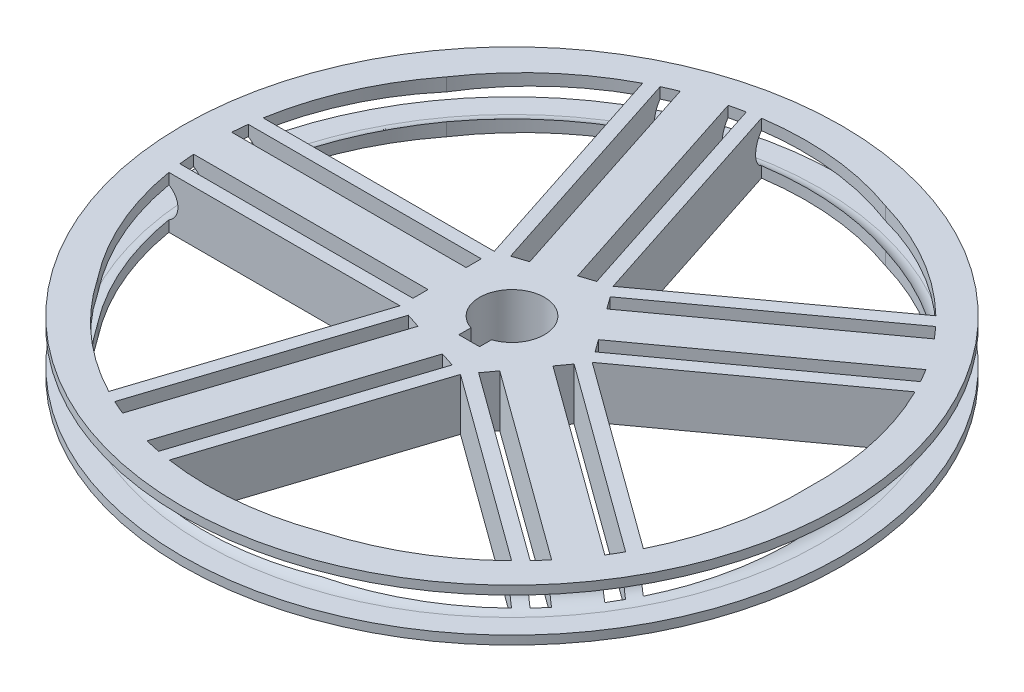
SolidWorks part; units mm, degrees
material "6061 Alloy"
ref_plane "Front Plane" through (0, 0, 0) normal (0, 0, 1) x (1, 0, 0)
ref_plane "Top Plane" through (0, 0, 0) normal (0, 1, 0) x (1, 0, 0)
ref_plane "Right Plane" through (0, 0, 0) normal (1, 0, 0) x (0, 0, -1)
sketch "Sketch1" plane through (0, 0, 0) normal (0, 0, 1) x (1, 0, 0)
  line L3 (0, 8) -> (-5, 8)
  line L4 (0, 0) -> (-5, 0)
  line L5 (-5, 8) -> (-5, 10)
  line L6 (-5, 10) -> (71.2, 10)
  line L7 (0, 4) -> (7.1457, 4) construction
  line L8 (-5, 0) -> (-5, -2)
  line L9 (-5, -2) -> (71.2, -2)
  line L10 (71.2, 10) -> (71.2, -2)
  arc A1 (0, 8) -> (0, 0) centre (0, 4) cw
  dimension "D2" = 4
  dimension "D1" = 8
  dimension "D3" = 5
  dimension "D4" = 5
  dimension "D5" = 76.2
  dimension "D6" = 2
revolve "Revolve2" add sketch "Sketch1" angle 360 about L10
sketch "Sketch2" plane through (0, -2, 0) normal (0, -1, 0) x (1, 0, 0)
  line L5 (71.2, 0) -> (128.6984, 0) construction
  circle A0 centre (71.2, 0) radius 7.5
  dimension "D1" = 15
extrude "Cut-Extrude3" cut sketch "Sketch2" against normal through all
sketch "Sketch3" plane through (0, -2, 0) normal (0, -1, 0) x (1, 0, 0)
  line L0 (71.2, 0) -> (130.5671, 0) construction
  line L2 (89.741, 0) -> (76.9295, 17.6336)
  line L3 (76.9295, 17.6336) -> (56.2, 10.8981)
  line L4 (56.2, 10.8981) -> (56.2, -10.8981)
  line L5 (56.2, -10.8981) -> (76.9295, -17.6336)
  line L6 (76.9295, -17.6336) -> (89.741, 0)
  line L7 (71.2, 0) -> (76.9295, 17.6336)
  line L8 (76.9295, 17.6336) -> (92.3803, 65.1864)
  line L9 (71.2, 0) -> (89.741, 0)
  line L10 (89.741, 0) -> (139.741, 0)
  line L11 (80.7501, 12.3749) -> (124.5759, 44.2162)
  line L12 (85.9204, 5.2586) -> (129.7462, 37.0999)
  line L13 (76.9295, 17.6336) -> (120.1357, 49.0247)
  line L14 (78.6928, 15.2065) -> (122.2514, 46.8536)
  line L15 (89.741, 0) -> (132.9473, 31.3912)
  line L16 (87.9777, 2.4271) -> (131.5362, 34.0742)
  circle A1 centre (71.2, 0) radius 15 construction
  arc A2 (92.3803, 65.1864) -> (139.741, 0) centre (74.3306, 2.2745) cw
  dimension "D5" = 90
  dimension "D6" = 90
  dimension "D7" = 6.5
  dimension "D1" = 30
  dimension "D4" = 65.45
  dimension "D2" = 50
  dimension "D3" = 50
  dimension "D8" = 6.5
  dimension "D9" = 3
  dimension "D10" = 90
  dimension "D11" = 3
sketch "Sketch5" plane through (0, -2, 0) normal (0, -1, 0) x (1, 0, 0)
  line L0 (71.2, 0) -> (71.2, 9.89)
  line L1 (68.81, 9.89) -> (73.59, 9.89)
  line L4 (71.2, 9.89) -> (71.2, 7.5)
  line L5 (68.81, 9.89) -> (68.81, 6.6936)
  line L6 (73.59, 9.89) -> (73.59, 6.6936)
  line L7 (68.81, 6.6936) -> (73.59, 6.6936)
  circle A1 centre (71.2, 0) radius 7.5 construction
  circle M28 centre (71.2, 0) radius 7.5
  dimension "D2" = 2.39
  dimension "D1" = 2.39
extrude "Cut-Extrude5" cut sketch "Sketch5" against normal through all contours L1 L0 M28 | L6 L1 L0 M28 | L0 M28 | L0 L6 M28 region at (69.9743, -2, 8.6279) region at (72.2807, -2, 7.0423) region at (72.4257, -2, 8.6279) region at (70.1193, -2, 7.0423)
extrude "Cut-Extrude7" cut sketch "Sketch3" against normal through all both and the other way through all contours A2 L8 L13 | A2 L14 L2 L11 | A2 L12 L2 L16 | A2 L15 L10 region at (121.6569, -2, 10.7441) region at (108.8005, -2, 19.7211) region at (97.0103, -2, 44.6672) region at (101.5751, -2, 29.6661)
pattern_circular "CirPattern1" count 5 over 360 about axis through (71.2, -2, 0) along (0, -1, 0) of "Cut-Extrude7"
